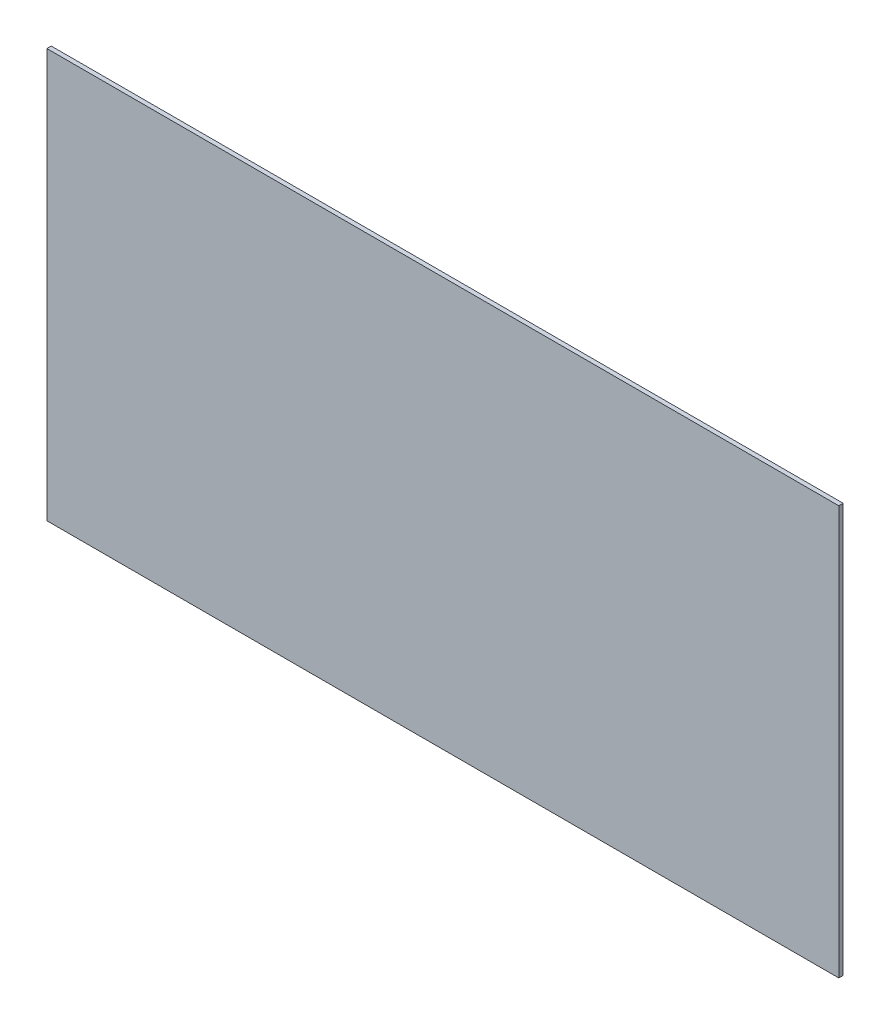
SolidWorks part; units mm, degrees
material "Acrylic (Medium-high impact)"
ref_plane "Front Plane" through (0, 0, 0) normal (0, 0, 1) x (1, 0, 0)
ref_plane "Top Plane" through (0, 0, 0) normal (0, 1, 0) x (1, 0, 0)
ref_plane "Right Plane" through (0, 0, 0) normal (1, 0, 0) x (0, 0, -1)
sketch "Sketch1" plane through (0, 0, 0) normal (0, 0, 1) x (1, 0, 0)
  line L1 (-289.5, -149.5) -> (289.5, -149.5)
  line L2 (-289.5, -149.5) -> (-289.5, 149.5)
  line L3 (-289.5, 149.5) -> (289.5, 149.5)
  line L4 (289.5, -149.5) -> (289.5, 149.5)
  line L5 (-289.5, -149.5) -> (289.5, 149.5) construction
  line L6 (-289.5, 149.5) -> (289.5, -149.5) construction
  point P0 (0, 0)
  dimension "D1" = 579
  dimension "D2" = 299
extrude "Boss-Extrude1" add sketch "Sketch1" along normal mid plane 3.175
